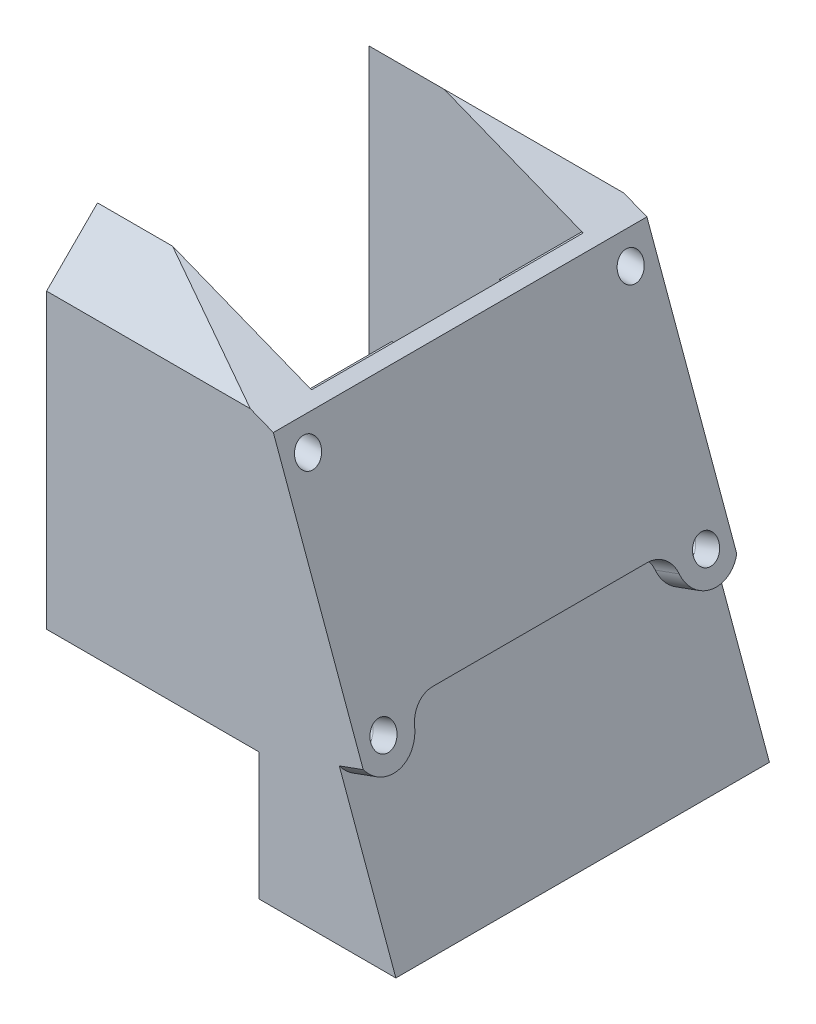
SolidWorks part; units mm, degrees
ref_plane "Front Plane" through (0, 0, 0) normal (0, 0, 1) x (1, 0, 0)
ref_plane "Top Plane" through (0, 0, 0) normal (0, 1, 0) x (1, 0, 0)
ref_plane "Right Plane" through (0, 0, 0) normal (1, 0, 0) x (0, 0, -1)
sketch "Sketch1" plane through (0, 0, 0) normal (0, 0, 1) x (1, 0, 0)
  line L0 (-25, 22) -> (1.7101, 11.4259)
  line L1 (0, 16.1243) -> (54.7232, -134.2265) construction
  line L2 (1.7101, 11.4259) -> (19.3357, -37)
  line L3 (19.3357, -37) -> (2.5, -37)
  line L4 (2.5, -55.7) -> (2.5, -23) construction
  line L5 (2.5, -37) -> (2.5, -22)
  line L6 (2.5, -22) -> (-25, -22)
  line L7 (-25, -22) -> (-25, 22)
  dimension "D1" = 15
  dimension "D2" = 5
extrude "Boss-Extrude1" add sketch "Sketch1" along normal up to surface (6 mm away)
sketch "Sketch2" plane through (-25, 0, 0) normal (-1, 0, 0) x (0, 0, 1)
  line L0 (6, 12.5) -> (-3.5, 22) construction
  line L1 (0, 22) -> (0, -22) construction
  line L2 (6, 22) -> (0, 22) construction
  line L3 (6, -22) -> (6, 22) construction
  line L4 (6, 12.5) -> (-3.5, 22)
  line L5 (0, 22) -> (0, -22)
  line L6 (6, 22) -> (0, 22)
  line L7 (6, -22) -> (6, 22)
  line M2 (6, -22) -> (6, 22)
  line M3 (6, 22) -> (0, 22)
  line M4 (0, 22) -> (0, -22)
extrude "Cut-Extrude1" cut sketch "Sketch2" against normal through all contours L4 M2 M3 M4 region at (-25, 18.5192, 3.4615)
sketch "Sketch3" plane through (0, 0, 0) normal (0, 0, -1) x (-1, 0, 0)
  line L0 (-19.3357, -37) -> (-1.7101, 11.4259) construction
  line L1 (-1.7101, 11.4259) -> (16.159, 18.5) construction
  line L2 (-0.2, 14.65) -> (-0.2, 1.35) construction
  line L3 (0, -23) -> (0, 18) construction
  line L4 (25, -22) -> (-2.5, -22) construction
  line L5 (-2.5, -22) -> (-2.5, -37) construction
  line L6 (-2.5, -37) -> (-19.3357, -37) construction
  line L7 (-19.3357, -37) -> (-1.7101, 11.4259)
  line L8 (-1.7101, 11.4259) -> (16.159, 18.5)
  line L9 (-0.2, 14.65) -> (-0.2, 1.35)
  line L10 (0, -23) -> (0, 18)
  line L11 (25, -22) -> (-2.5, -22)
  line L12 (-2.5, -22) -> (-2.5, -37)
  line L13 (-2.5, -37) -> (-19.3357, -37)
  line L14 (-0.2, 1.35) -> (0, 1.35)
  line M3 (-1.7101, 11.4259) -> (-19.3357, -37)
  line M4 (-19.3357, -37) -> (-2.5, -37)
  line M5 (-2.5, -37) -> (-2.5, -22)
  line M6 (-2.5, -22) -> (25, -22)
extrude "Boss-Extrude2" add sketch "Sketch3" along normal up to surface (32 mm away) contours L14 L9 L8 L10 M3 M4 M5 M6 region at (6.9311, -18.8343, 0)
sketch "Sketch4" plane through (0.2, 0, 0) normal (-1, 0, 0) x (0, 0, 1)
  line L0 (-32, 1.35) -> (0, 1.35) construction
  line L1 (0, 18.5) -> (0, -22) construction
  line L2 (-32, 12.0237) -> (0, 12.0237) construction
  line L3 (-32, 1.35) -> (-32, 12.0237) construction
  line L4 (-32, 1.35) -> (0, 1.35)
  line L5 (0, 18.5) -> (0, -22)
  line L6 (-32, 12.0237) -> (0, 12.0237)
  line L7 (-32, 1.35) -> (-32, 12.0237)
  circle A0 centre (-16, 8) radius 7.5
  line M1 (-32, 12.0237) -> (-32, 1.35)
  line M2 (-32, 1.35) -> (0, 1.35)
  line M3 (0, 1.35) -> (0, 12.0237)
  line M4 (0, 12.0237) -> (-32, 12.0237)
  dimension "D1" = 15
extrude "Boss-Extrude3" add sketch "Sketch4" along normal up to surface (0.2 mm away) contours A0 M4 M1 M2 | A0 M2 M3 M4 region at (0.2, 6.4625, -27.2671) region at (0.2, 6.4625, -4.7329) up to face at (0, -13.2437, -20)
sketch "Sketch5" plane through (0, -22, 0) normal (0, -1, 0) x (1, 0, 0)
  line L0 (0, -32) -> (0, 0) construction
  line L1 (0, -32) -> (0, 0)
  line L2 (0, 0) -> (0, 6)
  line L3 (2.5, 6) -> (-25, 6) construction
  line L4 (0, 6) -> (2.5, 6)
  line L5 (2.5, 6) -> (2.5, -32)
  line L6 (2.5, -32) -> (0, -32)
  arc A0 (-11.6056, -25.8586) -> (-21.8586, -15.6056) centre (-9.75, -13.75) ccw construction
  arc A1 (-11.6056, -25.8586) -> (-21.8586, -15.6056) centre (-9.75, -13.75) ccw
  line M1 (2.5, -32) -> (2.5, 6)
  line M2 (2.5, 6) -> (-25, 6)
  line M5 (0, 0) -> (0, -32)
  line M6 (0, -32) -> (2.5, -32)
extrude "Boss-Extrude4" add sketch "Sketch5" along normal up to surface (15 mm away) contours A1 L5 L2 M2 M5 | A1 M5 M6 M1 region at (1.3422, -22, -25.289) region at (1.3328, -22, -1.4494) up to face at (10.9178, -37, -13)
sketch "Sketch6" plane through (0, 0, -32) normal (0, 0, -1) x (-1, 0, 0)
  line L6 (25, 22) -> (-1.7101, 11.4259)
  line L7 (-1.7101, 11.4259) -> (-19.3357, -37)
  line L8 (-19.3357, -37) -> (-2.5, -37)
  line L9 (-2.5, -37) -> (-2.5, -22)
  line L10 (-2.5, -22) -> (25, -22)
  line L11 (25, -22) -> (25, 22)
  line L12 (25, 22) -> (-1.7101, 11.4259)
  line L13 (-1.7101, 11.4259) -> (-19.3357, -37)
  line L14 (-19.3357, -37) -> (-2.5, -37)
  line L15 (-2.5, -37) -> (-2.5, -22)
  line L16 (-2.5, -22) -> (25, -22)
  line L17 (25, -22) -> (25, 22)
  dimension "D1" = 0
extrude "Boss-Extrude5" add sketch "Sketch6" along normal up to surface (6 mm away)
sketch "Sketch7" plane through (-25, 0, 0) normal (-1, 0, 0) x (0, 0, 1)
  line L0 (-38, 22) -> (-32, 22)
  line L1 (-32, 22) -> (-32, 18.5)
  line L2 (-32, -22) -> (-32, 22) construction
  line L3 (-32, 18.5) -> (-38, 12.5)
  line L4 (-38, 22) -> (-38, -22) construction
  line L5 (-28.5, 22) -> (-38, 12.5) construction
  line L6 (-38, 12.5) -> (-38, 22)
extrude "Cut-Extrude2" cut sketch "Sketch7" against normal through all
sketch "Sketch8" plane through (-25, 0, 0) normal (-1, 0, 0) x (0, 0, 1)
  circle A0 centre (-35, 8.4289) radius 1.5 construction
  circle A1 centre (-35, -17) radius 1.5 construction
  circle A2 centre (3, -17) radius 1.5 construction
  circle A3 centre (3, 8.4289) radius 1.5 construction
  circle A4 centre (-35, 8.4289) radius 1.5
  circle A5 centre (-35, -17) radius 1.5
  circle A6 centre (3, -17) radius 1.5
  circle A7 centre (3, 8.4289) radius 1.5
extrude "Cut-Extrude3" cut sketch "Sketch8" against normal through all
sketch "Sketch9" plane through (0, -37, 0) normal (0, -1, 0) x (1, 0, 0)
  line L0 (-25, -38) -> (2.5, -38) construction
  line L1 (2.5, -32) -> (0, -32)
  line L2 (2.5, -32) -> (2.5, -38)
  line L3 (2.5, -38) -> (0, -38)
  line L4 (0, -32) -> (0, -38)
  line L5 (0, -32) -> (-25, -32) construction
  line L6 (0, -32) -> (0, -21.1662) construction
extrude "Boss-Extrude6" add sketch "Sketch9" against normal up to surface (15 mm away) up to face at (-9, -22, -34.4)
sketch "Sketch10" plane through (5.1823, 1.8862, 0) normal (0.9397, 0.342, 0) x (0, 0, -1)
  line L0 (38, -41.3818) -> (38, -17.3818)
  line L1 (38, -41.3818) -> (38, 10.1519) construction
  line L2 (38, -17.3818) -> (-6, -17.3818)
  line L3 (-6, 10.1519) -> (-6, -41.3818) construction
  line L4 (-6, -17.3818) -> (-6, -41.3818)
  line L5 (-6, -41.3818) -> (38, -41.3818)
  dimension "D1" = 24
extrude "Cut-Extrude4" cut sketch "Sketch10" against normal blind 3
sketch "Sketch11" plane through (2.3632, 0.8601, 0) normal (0.9397, 0.342, 0) x (0, 0, -1)
  line L0 (38, -17.3818) -> (-6, -17.3818) construction
  line L1 (-6, -17.3818) -> (-6, -40.2899) construction
  line L2 (38, -40.2899) -> (38, -17.3818) construction
  line L3 (38, -17.3818) -> (-6, -17.3818)
  line L4 (-6, -17.3818) -> (-6, -40.2899)
  line L5 (38, -40.2899) -> (38, -17.3818)
  circle A0 centre (-3, -19.0064) radius 3.5
  circle A1 centre (35, -19.0064) radius 3.5
  ellipse M1 centre (35, -19.0064) end of major axis (35, -17.4101) minor radius 1.5
  ellipse M2 centre (-3, -19.0064) end of major axis (-3, -17.4101) minor radius 1.5
  line M5 (38, -17.3818) -> (-6, -17.3818)
  line M6 (-6, -17.3818) -> (-6, -40.2899)
  dimension "D1" = 7
extrude "Boss-Extrude7" add sketch "Sketch11" along normal up to surface (3 mm away) contours A0 L3 M6 M2 | A1 L5 M5 M1 region at (8.8942, -17.0837, -37.9172) region at (8.5844, -16.2325, -0.3182) up to face at (2.2549, 9.9289, 3)
fillet "Fillet1" radius 3 2 edges at (9.7177, -14.9604, -31.8999) (9.7177, -14.9604, -0.1001)
